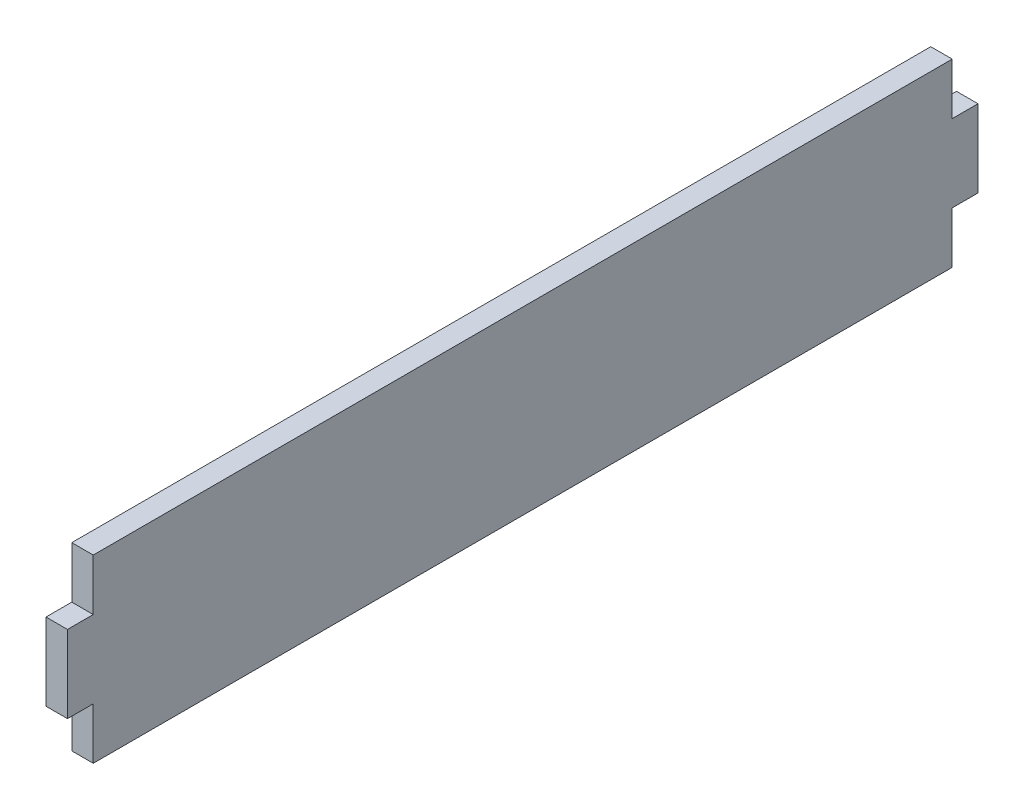
SolidWorks part; units mm, degrees
ref_plane "Front Plane" through (0, 0, 0) normal (0, 0, 1) x (1, 0, 0)
ref_plane "Top Plane" through (0, 0, 0) normal (0, 1, 0) x (1, 0, 0)
ref_plane "Right Plane" through (0, 0, 0) normal (1, 0, 0) x (0, 0, -1)
sketch "Sketch1" plane through (0, 0, 0) normal (0, 0, 1) x (1, 0, 0)
  line L0 (0, 6) -> (0, -6) construction
  line L1 (-1.25, 10.5) -> (1.25, 10.5)
  line L2 (-1.25, 10.5) -> (-1.25, -10.5)
  line L3 (-1.25, -10.5) -> (1.25, -10.5)
  line L4 (1.25, 10.5) -> (1.25, -10.5)
  line L5 (-1.25, 10.5) -> (1.25, -10.5) construction
  line L6 (-1.25, -10.5) -> (1.25, 10.5) construction
  line L7 (1.25, 4.5) -> (1.25, -4.5)
  line L8 (-1.25, 4.5) -> (-1.25, -4.5)
  line L9 (-1.25, 4.5) -> (1.25, 4.5)
  line L10 (1.25, -4.5) -> (-1.25, -4.5)
  point P0 (0, 0)
  point P8 (0, 0)
  dimension "D1" = 2.5
  dimension "D2" = 21
  dimension "D3" = 2.5
  dimension "D4" = 9
  dimension "D5" = 4.5
extrude "Boss-Extrude1" add sketch "Sketch1" along normal blind 100 contours L4 L1 L2 | L2 L3 L4 | L2 L4 region at (0, 7.5, 0) region at (0, 0, 0) region at (0, -7.5, 0)
extrude "Boss-Extrude2" add sketch "Sketch1<3>" against normal blind 3 contours L2 L4 region at (0, 0, 0)
sketch "Sketch1<3>" plane through (0, 0, 0) normal (0, 0, 1) x (1, 0, 0) same geometry as "Sketch1"
ref_plane "Plane1" through (0, 0, 50) normal (0, 0, -1) x (-1, 0, 0)
mirror "Mirror1" about plane through (0, 0, 50) normal (0, 0, -1) of "Boss-Extrude2"
